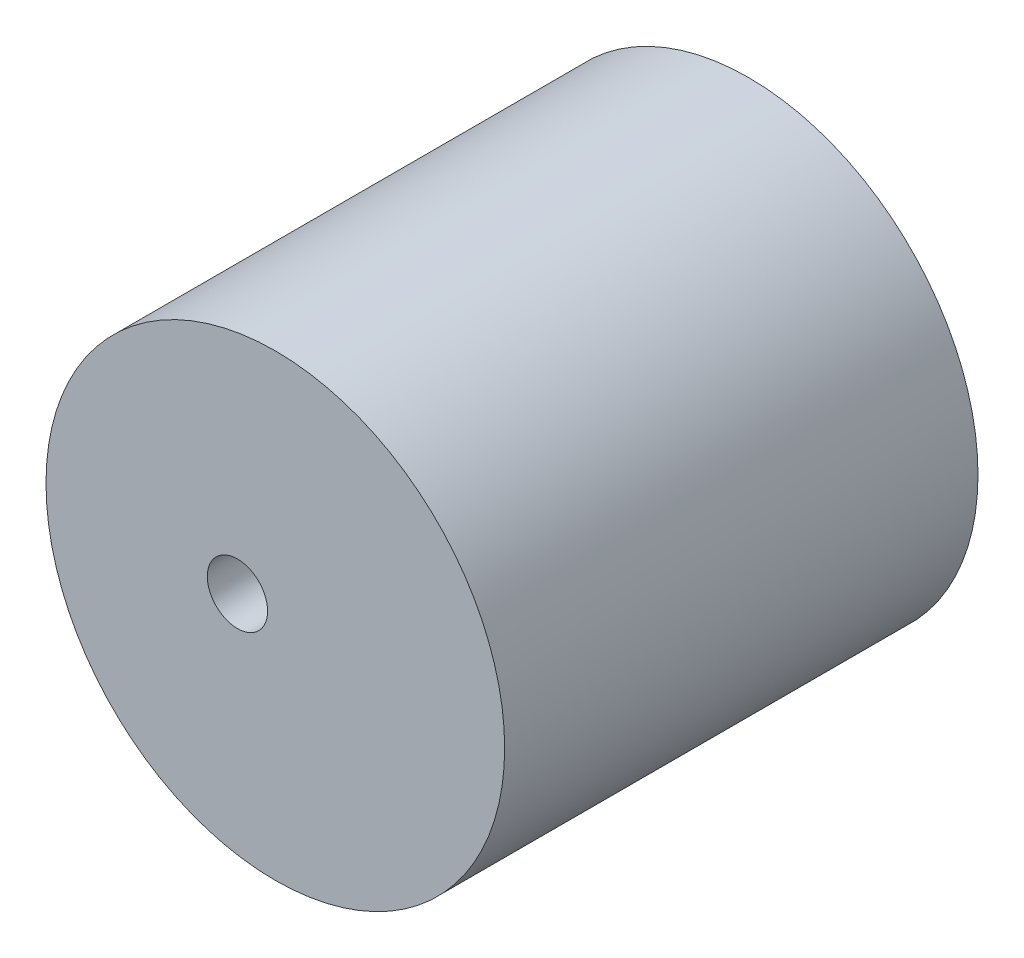
SolidWorks part; units mm, degrees
ref_plane "Front Plane" through (0, 0, 0) normal (0, 0, 1) x (1, 0, 0)
ref_plane "Top Plane" through (0, 0, 0) normal (0, 1, 0) x (1, 0, 0)
ref_plane "Right Plane" through (0, 0, 0) normal (1, 0, 0) x (0, 0, -1)
sketch "Sketch1" plane through (0, 0, 0) normal (0, 0, 1) x (1, 0, 0)
  circle A0 centre (0, 0) radius 24.225
  circle A2 centre (-4, 0) radius 3.185
extrude "Boss-Extrude5" add sketch "Sketch1" along normal blind 50 contours A2 | A0 region at (-4, 0, 0)
sketch "Sketch2" plane through (0, 0, 0) normal (0, 0, 1) x (1, 0, 0)
  circle A0 centre (0, 0) radius 23.75
sketch "Sketch3" plane through (0, 0, 0) normal (0, 0, 1) x (1, 0, 0)
  circle A0 centre (-4, 0) radius 3.175
sketch "Sketch4" plane through (0, 0, 0) normal (0, 0, 1) x (1, 0, 0)
  circle A0 centre (0, 0) radius 23.3344
sketch "Sketch5" plane through (0, 0, 0) normal (0, 0, 1) x (1, 0, 0)
  circle A0 centre (0, 0) radius 23.3938
sketch "Sketch6" plane through (0, 0, 0) normal (0, 0, 1) x (1, 0, 0)
  circle A0 centre (0, 0) radius 23.4531
  circle A1 centre (-4, 0) radius 3.2906
extrude "Boss-Extrude9" add sketch "Sketch6" along normal blind 2
sketch "Sketch7" plane through (0, 0, 0) normal (0, 0, 1) x (1, 0, 0)
  circle A0 centre (0, 0) radius 24.1656
  circle A1 centre (-4, 0) radius 3.3069
extrude "Boss-Extrude10" add sketch "Sketch7" along normal blind 2
